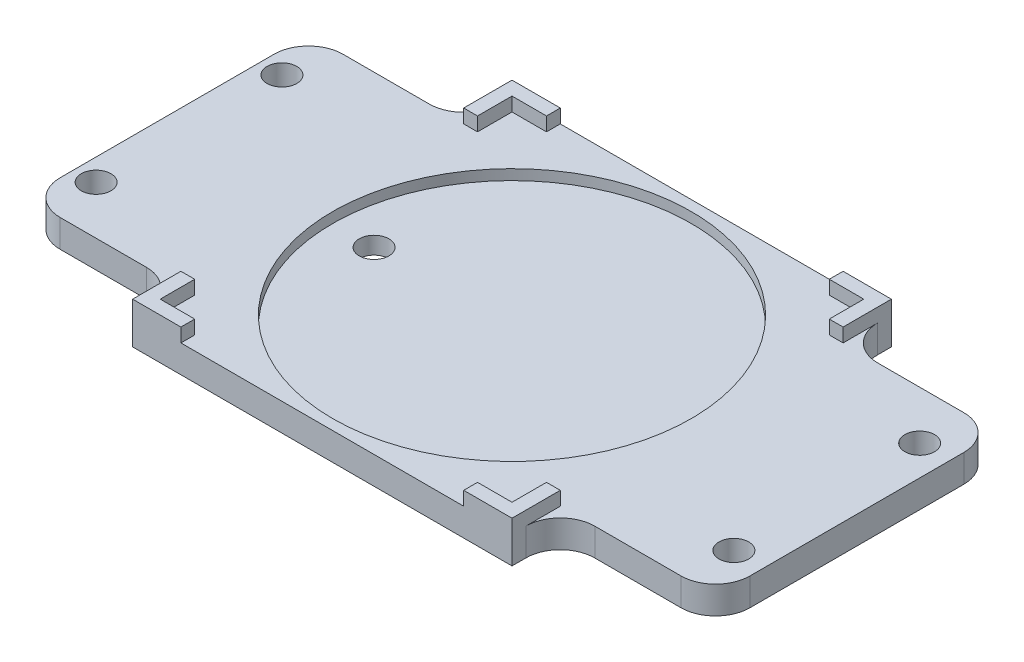
SolidWorks part; units mm, degrees
ref_plane "Front Plane" through (0, 0, 0) normal (0, 0, 1) x (1, 0, 0)
ref_plane "Top Plane" through (0, 0, 0) normal (0, 1, 0) x (1, 0, 0)
ref_plane "Right Plane" through (0, 0, 0) normal (1, 0, 0) x (0, 0, -1)
sketch "Sketch1" plane through (0, 0, 0) normal (0, 1, 0) x (1, 0, 0)
  line L1 (-50, 27.5) -> (50, 27.5)
  line L2 (-50, 27.5) -> (-50, -27.5)
  line L3 (-50, -27.5) -> (50, -27.5)
  line L4 (50, 27.5) -> (50, -27.5)
  line L5 (-50, 27.5) -> (50, -27.5) construction
  line L6 (-50, -27.5) -> (50, 27.5) construction
  point P0 (0, 0)
  dimension "D1" = 55
  dimension "D2" = 100
extrude "Boss-Extrude1" add sketch "Sketch1" along normal blind 4
hole_wizard "#6 Clearance Hole1" positions "Sketch2" profile "Sketch3" hole size "#6" standard "ANSI Inch" end condition through all
sketch "Sketch2" plane through (0, 4, 0) normal (0, 1, 0) x (1, 0, 0)
  arc A0 (45.6352, 12.1178) -> (45.6352, 14.8229) centre (45.6352, 13.4704) ccw construction
  arc A1 (45.6352, -14.8229) -> (45.6352, -12.1178) centre (45.6352, -13.4704) ccw construction
  arc A2 (-46.825, 14.8229) -> (-46.825, 12.1178) centre (-46.825, 13.4704) ccw construction
  arc A3 (-46.825, -12.1178) -> (-46.825, -14.8229) centre (-46.825, -13.4704) ccw construction
  point P0 (45.6352, 13.4704)
  point P2 (45.6352, -13.4704)
  point P4 (-46.825, -13.4704)
  point P6 (-46.825, 13.4704)
  point P23 (-20, 0)
  point P27 (0, 0)
  dimension "D1" = 20
sketch "Sketch3" plane through (45.6352, 4, -13.4704) normal (1, 0, 0) x (0, 0, 1)
  line L0 (0, 0) -> (0, 4)
  line L1 (0, 4) -> (2.1526, 4)
  line L2 (2.1526, 4) -> (2.1526, 0)
  line L5 (2.1526, 0) -> (0, 0)
  line L11 (0, -6.35) -> (0, 107.95) construction
  dimension "Thru Hole Dia." = 4.3053
  dimension "Thru Hole Depth" = 4
sketch "Sketch4" plane through (0, 4, 0) normal (0, 1, 0) x (1, 0, 0)
  circle A0 centre (0, 0) radius 26
  dimension "D1" = 52
extrude "Cut-Extrude1" cut sketch "Sketch4" against normal blind 1.5
sketch "Sketch6" plane through (0, 4, 0) normal (0, 1, 0) x (1, 0, 0)
  line L0 (-20.5, 25.5) -> (-20.5, 27.5)
  line L2 (50, 27.5) -> (-50, 27.5) construction
  line L3 (-20.5, 27.5) -> (-27.5, 27.5)
  line L4 (-27.5, 27.5) -> (-27.5, 20.5)
  line L5 (-27.5, 20.5) -> (-25.5, 20.5)
  line L7 (-25.5, 20.5) -> (-25.5, 25.5)
  line L8 (-25.5, 25.5) -> (-20.5, 25.5)
  point P2 (-25.8043, 25.9418)
  point P3 (0, 0)
  dimension "D1" = 5
extrude "Boss-Extrude2" add sketch "Sketch6" along normal blind 2
sketch "Sketch7" plane through (0, 4, 0) normal (0, 1, 0) x (1, 0, 0)
  line L1 (-50, 27.5) -> (-27.5, 27.5)
  line L2 (-50, 27.5) -> (-50, 20.5)
  line L3 (-50, 20.5) -> (-27.5, 20.5)
  line L4 (-27.5, 27.5) -> (-27.5, 20.5)
extrude "Cut-Extrude2" cut sketch "Sketch7" against normal up to next
mirror "Mirror1" about plane through (0, 0, 0) normal (0, 0, 1) of "Boss-Extrude2", "Cut-Extrude2"
mirror "Mirror2" about plane through (0, 0, 0) normal (1, 0, 0) of "Mirror1"
fillet "Fillet1" radius 5 8 edges at (-50, 2, -20.5) (-27.5, 2, -20.5) (50, 2, -20.5) (27.5, 2, -20.5) (50, 2, 20.5) (27.5, 2, 20.5) (-27.5, 2, 20.5) (-50, 2, 20.5)
equation "\"1é5\"=2"
